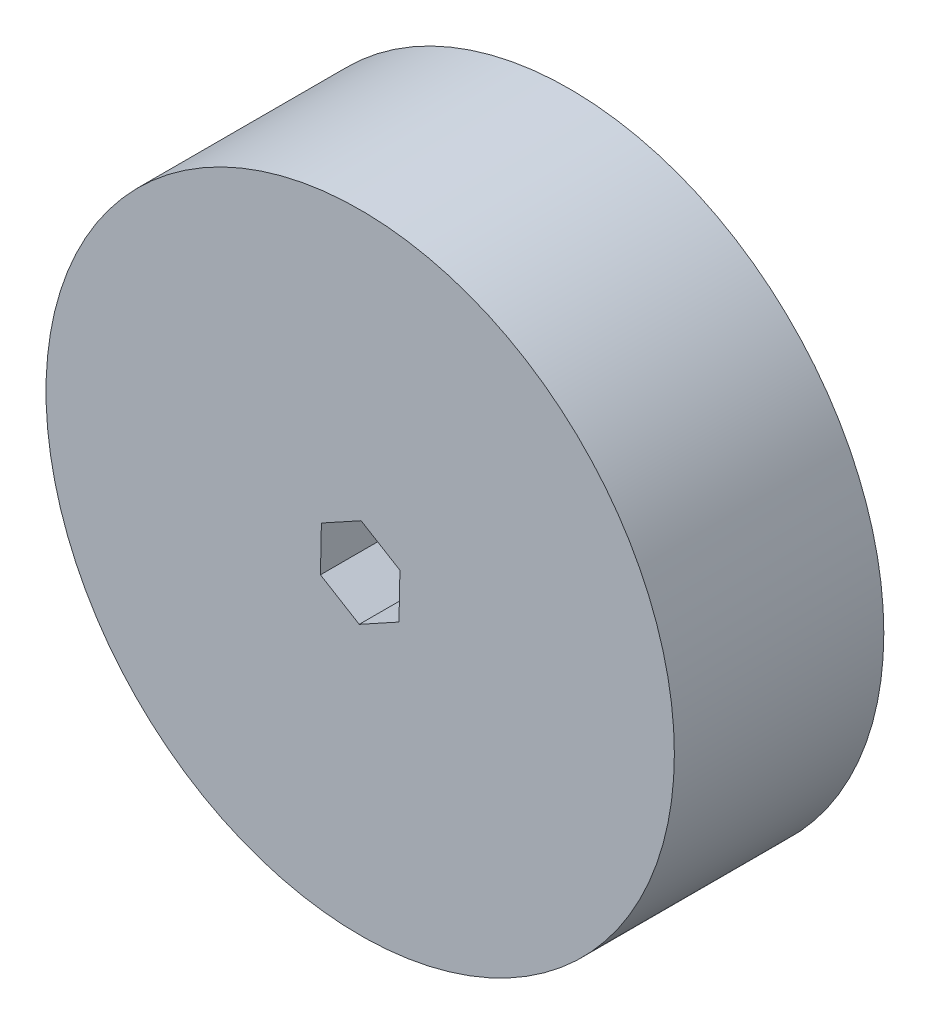
SolidWorks part; units mm, degrees
ref_plane "Front Plane" through (0, 0, 0) normal (0, 0, 1) x (1, 0, 0)
ref_plane "Top Plane" through (0, 0, 0) normal (0, 1, 0) x (1, 0, 0)
ref_plane "Right Plane" through (0, 0, 0) normal (1, 0, 0) x (0, 0, -1)
sketch "Sketch1" plane through (0, 0, 0) normal (0, 0, 1) x (1, 0, 0)
  line L1 (4.8185, 2.6502) -> (0.1141, 5.4981)
  line L2 (0.1141, 5.4981) -> (-4.7044, 2.8479)
  line L3 (-4.7044, 2.8479) -> (-4.8185, -2.6502)
  line L4 (-4.8185, -2.6502) -> (-0.1141, -5.4981)
  line L5 (-0.1141, -5.4981) -> (4.7044, -2.8479)
  line L6 (4.7044, -2.8479) -> (4.8185, 2.6502)
  circle A0 centre (0, 0) radius 38.1
  circle A1 centre (0, 0) radius 4.7625 construction
  dimension "D1" = 76.2
  dimension "D2" = 9.525
extrude "Boss-Extrude1" add sketch "Sketch1" along normal blind 25.4
